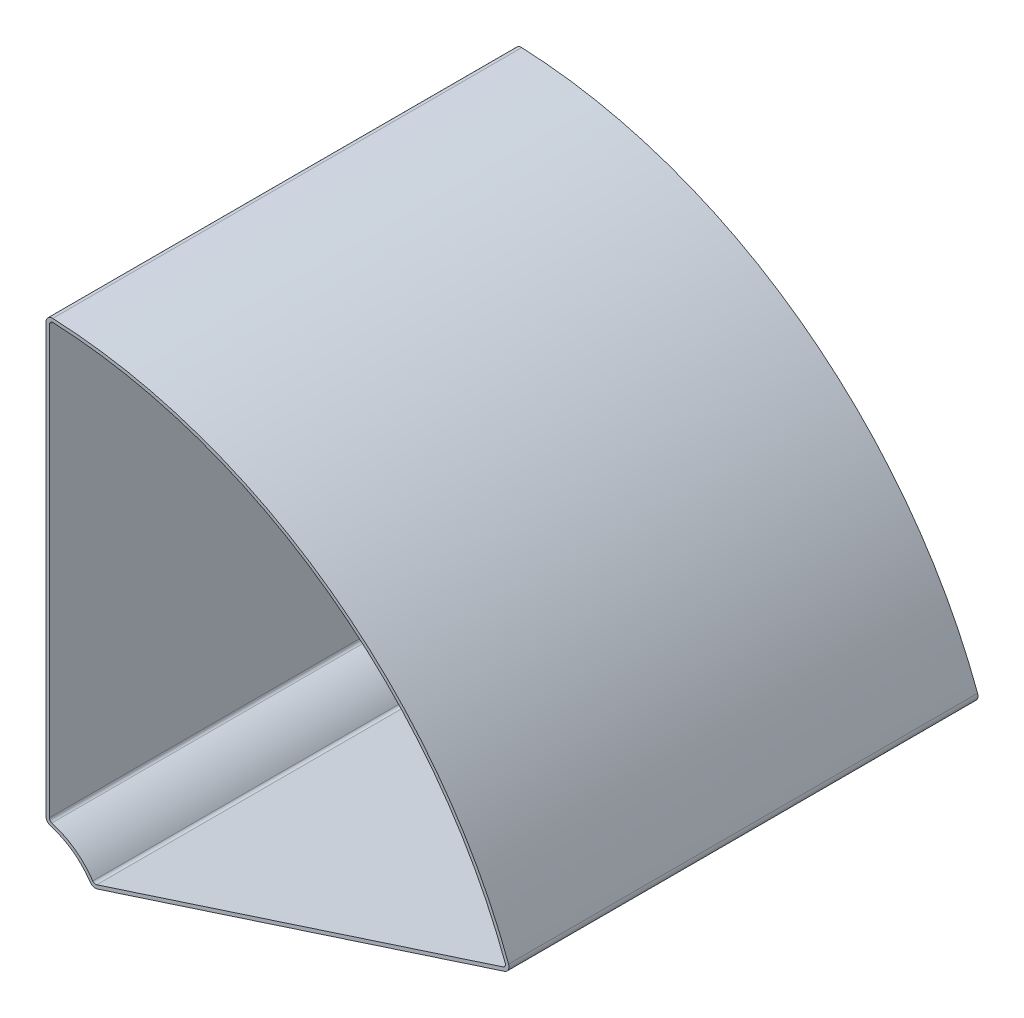
SolidWorks part; units mm, degrees
ref_plane "정면" through (0, 0, 0) normal (0, 0, 1) x (1, 0, 0)
ref_plane "윗면" through (0, 0, 0) normal (0, 1, 0) x (1, 0, 0)
ref_plane "우측면" through (0, 0, 0) normal (1, 0, 0) x (0, 0, -1)
sketch "스케치1" plane through (0, 0, 0) normal (0, 0, 1) x (1, 0, 0)
  line L0 (0, 239) -> (0, 0)
  line L1 (227.3025, 73.8551) -> (0, 0)
  line L2 (140.4807, -193.3551) -> (0, 0)
  line L3 (-140.4807, -193.3551) -> (0, 0)
  line L4 (-227.3025, 73.8551) -> (0, 0)
  line L5 (7, 239) -> (7, 0)
  line L6 (225.1394, 80.5125) -> (-2.1631, 6.6574)
  line L7 (8.6, 239) -> (8.6, 0)
  line L8 (224.645, 82.0341) -> (-2.6575, 8.1791)
  circle A0 centre (0, 0) radius 33.4
  circle A1 centre (0, 0) radius 35
  circle A2 centre (0, 0) radius 239
  circle A3 centre (0, 0) radius 237.4
  point P14 (0, 0)
  dimension "D1" = 66.8
  dimension "D2" = 70
  dimension "D3" = 478
  dimension "D4" = 1.6
  dimension "D6" = 7
  dimension "D7" = 7
  dimension "D8" = 1.6
  dimension "D9" = 1.6
  dimension "D5" = 5
extrude "보스-돌출1" add sketch "스케치1" along normal blind 220 contours A3 L7 A2 L5 | L7 A3 L5 A1 | A3 L8 A2 L7 | L7 A1 L5 A0 | L8 A1 L7 A0 | L6 A1 L8 A0 | L6 A3 L8 A1 | A3 L6 A2 L8 region at (7.8, 238.0718, 0) region at (7.8002, 135.6939, 0) region at (140.3236, 193.1389, 0) region at (7.8015, 33.2944, 0) region at (224.0094, 80.9865, 0) region at (19.6424, 27.0354, 0) region at (126.6422, 49.3502, 0) region at (29.254, 17.7082, 0)
extrude "보스-돌출2" add sketch "스케치1<3>" along normal blind 1.6 contours L8 A3 L7 A1 region at (91.194, 125.5178, 0)
sketch "스케치1<3>" plane through (0, 0, 0) normal (0, 0, 1) x (1, 0, 0) same geometry as "스케치1"
fillet "필렛1" radius 1.6 4 edges at (29.6089, 18.6631, 110.8) (8.6, 33.927, 110.8) (8.6, 237.2442, 110.8) (222.9751, 81.4916, 110.8)
fillet "필렛2" radius 3 4 edges at (28.8967, 16.7493, 110) (7, 32.6582, 110) (225.0419, 80.4808, 110) (7, 238.8975, 110)
